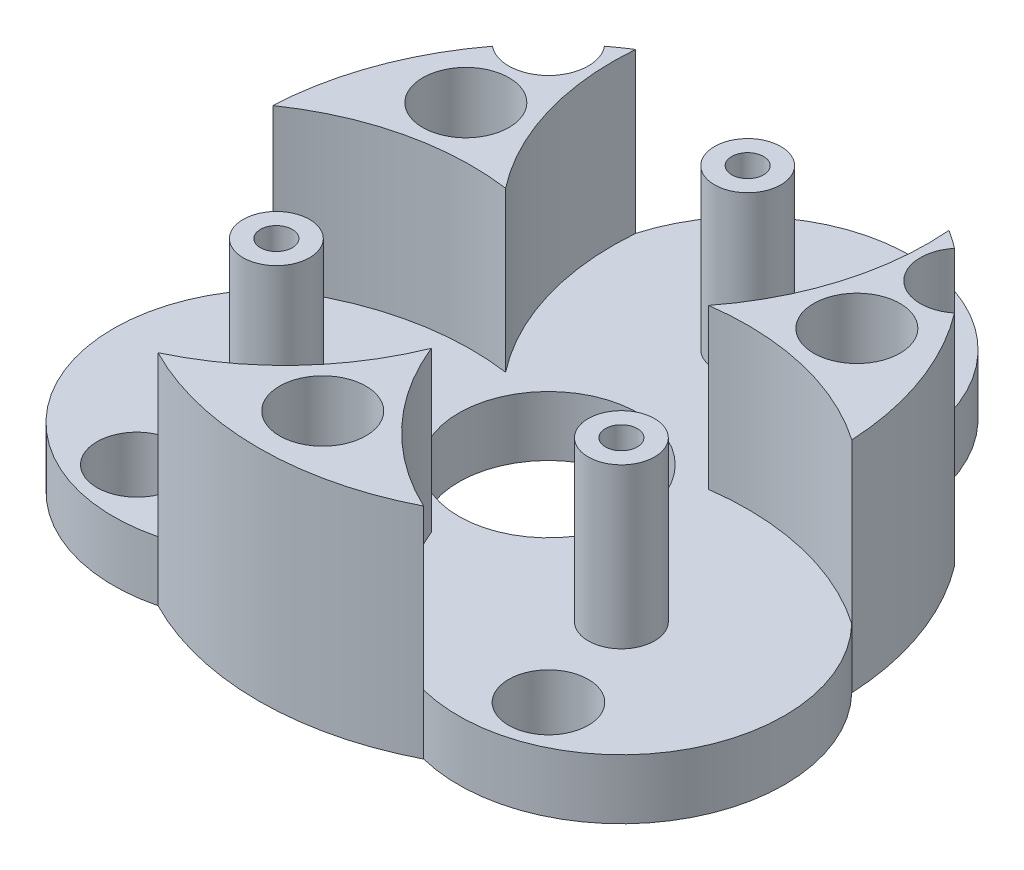
SolidWorks part; units mm, degrees
ref_plane "Alzado" through (0, 0, 0) normal (0, 0, 1) x (1, 0, 0)
ref_plane "Planta" through (0, 0, 0) normal (0, 1, 0) x (1, 0, 0)
ref_plane "Vista lateral" through (0, 0, 0) normal (1, 0, 0) x (0, 0, -1)
sketch "Croquis1" plane through (0, 0, 0) normal (0, 1, 0) x (1, 0, 0)
  circle A0 centre (0, 0) radius 5 construction
  circle A1 centre (0, 15) radius 10 construction
  circle A2 centre (0, 0) radius 25 construction
  circle A7 centre (0, 0) radius 21.825
  point P24 (0, 0)
  dimension "D1" = 10
  dimension "D2" = 20
  dimension "D3" = 43.65
extrude "Saliente-Extruir1" add sketch "Croquis1" along normal blind 4.5
sketch "Croquis2" plane through (0, 4.5, 0) normal (0, 1, 0) x (1, 0, 0)
  circle A0 centre (0, 0) radius 15 construction
  circle A1 centre (0, 15) radius 2.5
  circle A2 centre (12.9904, -7.5) radius 2.5
  circle A3 centre (-12.9904, -7.5) radius 2.5
  point P12 (0, 0)
  dimension "D1" = 30
  dimension "D2" = 5
  dimension "D3" = 3
extrude "Saliente-Extruir2" add sketch "Croquis2" along normal blind 12
hole_wizard "Taladro de margen para M121" positions "Croquis3" profile "Croquis4" hole size "M12" standard "ISO" end condition through all
sketch "Croquis3" plane through (0, 4.5, 0) normal (0, 1, 0) x (1, 0, 0)
  point P0 (0, 0)
sketch "Croquis4" plane through (0, 4.5, 0) normal (1, 0, 0) x (0, 0, 1)
  line L0 (0, 0) -> (0, 4.5)
  line L1 (0, 4.5) -> (6.75, 4.5)
  line L2 (6.75, 4.5) -> (6.75, 0)
  line L5 (6.75, 0) -> (0, 0)
  line L11 (0, -6.35) -> (0, 107.95) construction
  dimension "Diámetro de taladro hasta el siguiente" = 13.5
  dimension "Profundidad de taladro hasta el siguiente" = 4.5
sketch "Croquis5" plane through (0, 4.5, 0) normal (0, 1, 0) x (1, 0, 0)
  line L0 (0, 0) -> (-18.901, 10.9125) construction
  line L1 (-12.9904, -7.5) -> (0, 15) construction
  circle A0 centre (-12.9904, -7.5) radius 8.25 construction
  circle A1 centre (0, 15) radius 8.25 construction
  arc A4 (-7.6427, 4.4125) -> (-11.8002, 18.3599) centre (8.1271, 16.7067) cw
  arc A5 (-7.6427, 4.4125) -> (-21.8002, 1.0394) centre (-10.4048, -15.3916) ccw
  arc A6 (-11.8002, 18.3599) -> (-21.8002, 1.0394) centre (0, 0) ccw
  circle A7 centre (0, 0) radius 21.825 construction
  dimension "D1" = 20
  dimension "D2" = 13
extrude "Saliente-Extruir3" add sketch "Croquis5" along normal up to surface (12 mm away) up to face at (-12.9904, 16.5, 10)
sketch "Croquis8" plane through (0, 16.5, 0) normal (0, 1, 0) x (1, 0, 0)
  line L0 (-7.6427, 4.4125) -> (-18.901, 10.9125) construction
  circle A1 centre (-14.7224, 8.5) radius 1.7
  circle A2 centre (0, 0) radius 15 construction
  arc A3 (-11.8002, 18.3599) -> (-21.8002, 1.0394) centre (0, 0) ccw construction
  circle A4 centre (0, 0) radius 17 construction
  dimension "D1" = 3.4
  dimension "D2" = 2
extrude "Cortar-Extruir1" cut sketch "Croquis8" against normal up to surface (16.5 mm away) up to face at (0, 0, 6.75)
pattern_circular "MatrizC1" count 3 every 120 about axis through (0, 4.5, 0) along (0, 1, 0) of "Saliente-Extruir3", "Cortar-Extruir1"
hole_wizard "Taladro de margen para M21" positions "Croquis9" profile "Croquis10" hole size "M2" standard "ISO" end condition through all
sketch "Croquis9" plane through (0, 16.5, 0) normal (0, 1, 0) x (1, 0, 0)
  point P0 (12.9904, -7.5)
  point P4 (-12.9904, -7.5)
  point P7 (0, 15)
sketch "Croquis10" plane through (12.9904, 16.5, 7.5) normal (1, 0, 0) x (0, 0, 1)
  line L0 (0, 0) -> (0, 16.5)
  line L1 (0, 16.5) -> (1.2, 16.5)
  line L2 (1.2, 16.5) -> (1.2, 0)
  line L5 (1.2, 0) -> (0, 0)
  line L11 (0, -6.35) -> (0, 107.95) construction
  dimension "Diámetro de taladro hasta el siguiente" = 2.4
  dimension "Profundidad de taladro hasta el siguiente" = 16.5
sketch "Croquis11" plane through (0, 0, 0) normal (0, -1, 0) x (1, 0, 0)
  arc A0 (-10, 19.3992) -> (-21.8002, -1.0394) centre (0, 0) ccw construction
  arc A1 (-10, 19.3992) -> (-21.8002, -1.0394) centre (0, 0) ccw
  arc A2 (-21.8002, -1.0394) -> (-10, 19.3992) centre (-12.9904, 7.5) cw
  circle A3 centre (-12.9904, 7.5) radius 1.2 construction
  circle A4 centre (-12.9904, 7.5) radius 1.2 construction
extrude "Saliente-Extruir5" add sketch "Croquis11" against normal up to surface (4.5 mm away) up to face at (0, 4.5, 6.75)
pattern_circular "MatrizC2" count 3 every 120 about axis through (0, 0, 0) along (0, 1, 0) of "Saliente-Extruir5"
sketch "Croquis12" plane through (0, 0, 0) normal (0, -1, 0) x (1, 0, 0)
  circle A0 centre (-12.9904, 7.5) radius 2.875
  circle A1 centre (12.9904, 7.5) radius 2.875
  circle A2 centre (0, -15) radius 2.875
  point P10 (0, 0)
  dimension "D1" = 5.75
  dimension "D2" = 3
extrude "Cortar-Extruir2" cut sketch "Croquis12" against normal blind 2.2
sketch "Croquis13" plane through (0, 0, 0) normal (0, -1, 0) x (1, 0, 0)
  line L1 (15.5, -15.5) -> (-15.5, -15.5) construction
  line L2 (15.5, -15.5) -> (15.5, 15.5) construction
  line L3 (15.5, 15.5) -> (-15.5, 15.5) construction
  line L4 (-15.5, -15.5) -> (-15.5, 15.5) construction
  line L5 (15.5, -15.5) -> (-15.5, 15.5) construction
  line L6 (15.5, 15.5) -> (-15.5, -15.5) construction
  circle A0 centre (15.5, -15.5) radius 3
  circle A1 centre (-15.5, -15.5) radius 3
  circle A2 centre (-15.5, 15.5) radius 3
  circle A3 centre (15.5, 15.5) radius 3
  point P0 (0, 0)
  point P16 (0, 0)
  dimension "D2" = 6
  dimension "D1" = 31
  dimension "D3" = 4
extrude "Cortar-Extruir3" cut sketch "Croquis13" against normal up to surface (16.5 mm away) up to face at (-14.7224, 16.5, -6.8)
hole_wizard "Refrentado para tornillo con cabeza plana de M31" positions "Croquis14" profile "Croquis15" counterbore size "M3" standard "ISO" end condition through all
sketch "Croquis14" plane through (0, 16.5, 0) normal (0, 1, 0) x (1, 0, 0)
  point P0 (-14.7224, 8.5)
  point P3 (0, -17)
  point P6 (14.7224, 8.5)
sketch "Croquis15" plane through (-14.7224, 16.5, -8.5) normal (1, 0, 0) x (0, 0, 1)
  line L0 (0, 0) -> (0, 16.5)
  line L1 (0, 16.5) -> (1.7, 16.5)
  line L3 (1.7, 16.5) -> (1.7, 10)
  line L4 (1.7, 10) -> (3.25, 10)
  line L5 (3.25, 10) -> (3.25, 0)
  line L7 (3.25, 0) -> (0, 0)
  line L11 (0, -6.35) -> (0, 107.95) construction
  dimension "Diámetro de taladro hasta el siguiente" = 3.4
  dimension "Profundidad de taladro hasta el siguiente" = 16.5
  dimension "Diámetro de refrentado" = 6.5
  dimension "Profundidad de refrentado" = 10
